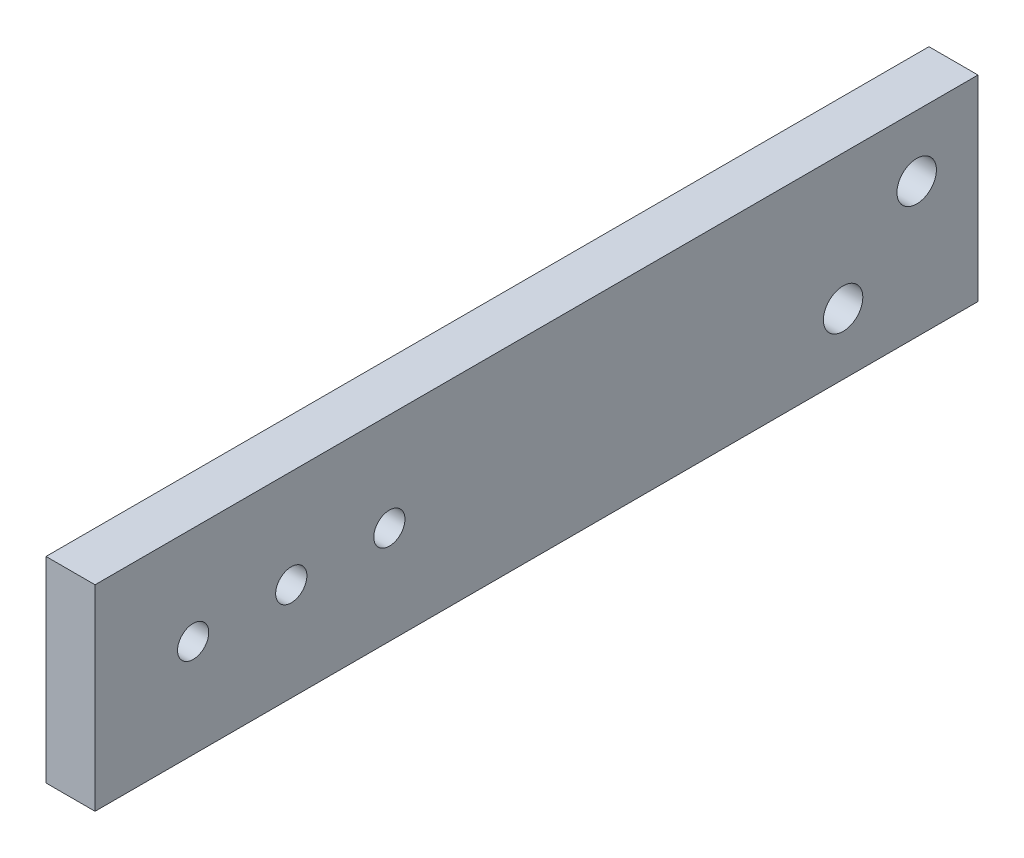
SolidWorks part; units mm, degrees
material "6061-T6 (SS)"
ref_plane "Front" through (0, 0, 0) normal (0, 0, 1) x (1, 0, 0)
ref_plane "Top" through (0, 0, 0) normal (0, 1, 0) x (1, 0, 0)
ref_plane "Right" through (0, 0, 0) normal (1, 0, 0) x (0, 0, -1)
sketch "Sketch1" plane through (0, 0, 0) normal (1, 0, 0) x (0, 0, -1)
  line L1 (0, 0) -> (114.3, 0)
  line L2 (0, 0) -> (0, 25.4)
  line L3 (0, 25.4) -> (114.3, 25.4)
  line L6 (114.3, 0) -> (114.3, 25.4)
  dimension "D1" = 25.4
  dimension "D4" = 114.3
extrude "Boss-Extrude1" add sketch "Sketch1" along normal blind 6.35
hole_wizard "#10-32 Tapped Hole1" positions "Sketch2" profile "Sketch3" tap size "#10-32" standard "ANSI Inch" end condition through all
sketch "Sketch2" plane through (6.35, 0, 0) normal (1, 0, 0) x (0, 0, -1)
  line L0 (0, 0) -> (12.7, 12.7) construction
  line L1 (12.7, 12.7) -> (25.4, 12.7) construction
  line L2 (25.4, 12.7) -> (38.1, 12.7) construction
  line L3 (38.1, 12.7) -> (50.8, 25.4) construction
  line L4 (114.3, 25.4) -> (0, 25.4) construction
  line L6 (0, 25.4) -> (0, 0) construction
  point P0 (12.7, 12.7)
  point P2 (25.4, 12.7)
  point P4 (38.1, 12.7)
  dimension "D1" = 50.8
  dimension "D2" = 12.7
sketch "Sketch3" plane through (6.35, 12.7, -12.7) normal (0, 1, 0) x (0, 0, -1)
  line L0 (0, 0) -> (0, 6.35)
  line L1 (0, 6.35) -> (2.0193, 6.35)
  line L2 (2.0193, 6.35) -> (2.0193, 0)
  line L5 (2.0193, 0) -> (0, 0)
  line L11 (0, -6.35) -> (0, 107.95) construction
  dimension "Thru Tap Drill Dia." = 4.0386
  dimension "Thru Tap Drill Depth" = 6.35
cosmetic thread "Hole Thread1" parameters "D2"=4.826
cosmetic thread "Hole Thread2" parameters "D2"=4.826
cosmetic thread "Hole Thread3" parameters "D2"=4.826
hole_wizard "#10 Clearance Hole1" positions "Sketch4" profile "Sketch5" hole size "#10" standard "ANSI Inch" end condition through all
sketch "Sketch4" plane through (6.35, 0, 0) normal (1, 0, 0) x (0, 0, -1)
  line L0 (88.9, 0) -> (96.8375, 7.9375) construction
  line L1 (0, 0) -> (114.3, 0) construction
  line L2 (96.8375, 7.9375) -> (106.3625, 17.4625) construction
  line L3 (106.3625, 17.4625) -> (114.3, 25.4) construction
  line L5 (114.3, 0) -> (114.3, 25.4) construction
  point P13 (106.3625, 17.4625)
  point P15 (96.8375, 7.9375)
  point P31 (97.0391, 6.7241)
  dimension "D1" = 25.4
  dimension "D2" = 9.525
sketch "Sketch5" plane through (6.35, 17.4625, -106.3625) normal (0, 1, 0) x (0, 0, -1)
  line L0 (0, 0) -> (0, 6.35)
  line L1 (0, 6.35) -> (2.5527, 6.35)
  line L2 (2.5527, 6.35) -> (2.5527, 0)
  line L5 (2.5527, 0) -> (0, 0)
  line L11 (0, -6.35) -> (0, 107.95) construction
  dimension "Thru Hole Dia." = 5.1054
  dimension "Thru Hole Depth" = 6.35
